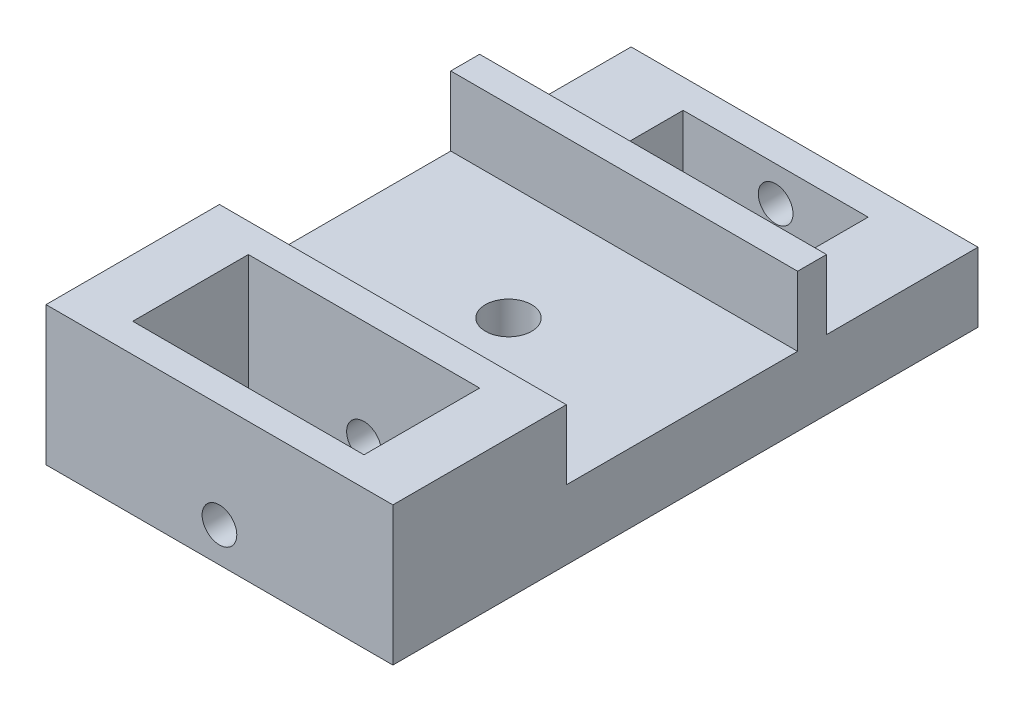
SolidWorks part; units mm, degrees
ref_plane "Front" through (0, 0, 0) normal (0, 0, 1) x (1, 0, 0)
ref_plane "Top" through (0, 0, 0) normal (0, 1, 0) x (1, 0, 0)
ref_plane "Right" through (0, 0, 0) normal (1, 0, 0) x (0, 0, -1)
sketch "Sketch1" plane through (0, 0, 0) normal (0, 1, 0) x (1, 0, 0)
  line L0 (0, -20) -> (0, -22.5)
  line L1 (0, 0) -> (-30, 0)
  line L2 (0, 0) -> (0, -20)
  line L3 (0, -20) -> (-30, -20)
  line L4 (-30, 0) -> (-30, -20)
  line L5 (0, -22.5) -> (-30, -22.5)
  line L6 (-30, -22.5) -> (-30, -20)
  line L7 (0, 0) -> (-7, 0)
  line L8 (-30, 0) -> (0, 0)
  line L9 (-30, 0) -> (-30, 2.5)
  line L10 (-30, 2.5) -> (0, 2.5)
  line L11 (0, 0) -> (0, 2.5)
  line L12 (-30, 0) -> (-23, 0)
  line L13 (-30, 2.5) -> (-30, 13.1)
  line L14 (-30, 13.1) -> (0, 13.1)
  line L15 (0, 13.1) -> (0, 2.5)
  line L16 (0, 13.1) -> (0, 15.6)
  line L17 (0, 15.6) -> (-30, 15.6)
  line L18 (-30, 15.6) -> (-30, 13.1)
  line L19 (-7, 0) -> (-7, 15.6)
  line L20 (-23, 0) -> (-23, 15.6)
  dimension "D1" = 20
  dimension "D2" = 2.5
  dimension "D3" = 2.5
  dimension "D4" = 30
  dimension "D5" = 7
  dimension "D6" = 7
  dimension "D7" = 10.6
  dimension "D8" = 2.5
extrude "Boss-Extrude1" add sketch "Sketch1" along normal blind 6 contours L1 L8 L4 L3 L2 | L6 L5 L0 L3 | L20 L1 L19 L10 | L19 L1 L11 L10 | L19 L10 L15 L14 | L19 L14 L16 L17 | L20 L14 L19 L17 | L14 L20 L17 L18 | L10 L20 L14 L13 | L8 L20 L10 L9 region at (-15, 0, 10) region at (-15, 0, 21.25) region at (-3.5, 0, -1.25) region at (-15, 0, -1.25) region at (-3.5, 0, -7.8) region at (-26.5, 0, -1.25) region at (-3.5, 0, -14.35) region at (-26.5, 0, -7.8) region at (-15, 0, -14.35) region at (-26.5, 0, -14.35)
extrude "Boss-Extrude2" add sketch "Sketch1<3>" along normal blind 12 contours L19 L1 L11 L10 | L20 L1 L19 L10 | L6 L5 L0 L3 | L8 L20 L10 L9 region at (-15, 0, 21.25) region at (-3.5, 0, -1.25) region at (-15, 0, -1.25) region at (-26.5, 0, -1.25)
sketch "Sketch1<3>" plane through (0, 0, 0) normal (0, 1, 0) x (1, 0, 0) same geometry as "Sketch1"
sketch "Sketch3" plane through (0, 0, -15.6) normal (0, 0, -1) x (-1, 0, 0)
  line L0 (30, 3) -> (23, 3)
  line L1 (30, 6) -> (30, 0) construction
  line L2 (23, 3) -> (15, 3)
  circle A0 centre (15, 3) radius 1.5
  dimension "D1" = 7
  dimension "D2" = 8
extrude "Cut-Extrude2" cut sketch "Sketch3" against normal blind 5 contours A0
sketch "Sketch4" plane through (0, 0, -2.5) normal (0, 0, -1) x (-1, 0, 0)
  line L0 (23, 3) -> (15, 3)
  line L1 (23, 6) -> (23, 0) construction
  line L3 (17.8868, 3) -> (16.4434, 5.5)
  line L4 (16.4434, 5.5) -> (13.5566, 5.5)
  line L5 (13.5566, 5.5) -> (12.1132, 3)
  line L6 (12.1132, 3) -> (13.5566, 0.5)
  line L7 (13.5566, 0.5) -> (16.4434, 0.5)
  line L8 (16.4434, 0.5) -> (17.8868, 3)
  circle A0 centre (15, 3) radius 2.5 construction
  dimension "D1" = 8
extrude "Cut-Extrude3" cut sketch "Sketch4" against normal blind 2.5 contours L7 L8 L3 L4 L5 L6 region at (-17.0989, 1.7882, -2.5)
ref_plane "Plane1" through (0, 0, 10) normal (0, 0, -1) x (-1, 0, 0)
sketch "Sketch2" plane through (0, 6, 0) normal (0, 1, 0) x (1, 0, 0)
  line L0 (-30, -10) -> (0, -10)
  line L1 (-30, 0) -> (-30, -20) construction
  line L2 (0, 0) -> (0, -20) construction
  circle A0 centre (-15, -10) radius 2
extrude "Cut-Extrude1" cut sketch "Sketch2" against normal through all contours L0 A0 | L0 A0 region at (-15, 6, 9.1512) region at (-15, 6, 10.8488)
sketch "Sketch5" plane through (0, 0, 0) normal (0, -1, 0) x (1, 0, 0)
  line L0 (-30, 22.5) -> (-25, 22.5)
  line L1 (-30, 22.5) -> (0, 22.5)
  line L2 (-30, 22.5) -> (-30, 32.5)
  line L3 (0, 22.5) -> (0, 32.5)
  line L4 (-30, 32.5) -> (0, 32.5)
  line L5 (-25, 22.5) -> (-25, 32.5)
  line L6 (-25, 32.5) -> (-5, 32.5)
  line L7 (-5, 32.5) -> (-5, 22.5)
  line L8 (-5, 22.5) -> (0, 22.5)
  line L9 (-30, 32.5) -> (-30, 35)
  line L10 (-30, 35) -> (0, 35)
  line L11 (0, 35) -> (0, 32.5)
  line M7 (0, 22.5) -> (-30, 22.5)
  dimension "D1" = 10
  dimension "D2" = 5
  dimension "D3" = 5
  dimension "D4" = 2.5
extrude "Boss-Extrude3" add sketch "Sketch5" against normal blind 12 contours L5 L4 L2 M7 | L11 L10 L9 L4 | L4 L7 L3 M7 region at (-27.5, 0, 27.5) region at (-15, 0, 33.75) region at (-2.5, 0, 27.5)
sketch "Sketch6" plane through (0, 0, 35) normal (0, 0, 1) x (1, 0, 0)
  line L0 (0, 0) -> (0, 6)
  line L1 (0, 12) -> (0, 0) construction
  line L2 (0, 6) -> (0, 3)
  line L3 (0, 3) -> (-15, 3)
  circle A1 centre (-15, 3) radius 1.5
extrude "Cut-Extrude4" cut sketch "Sketch6" against normal blind 20 contours A1 region at (-16.4576, 3, 35)
